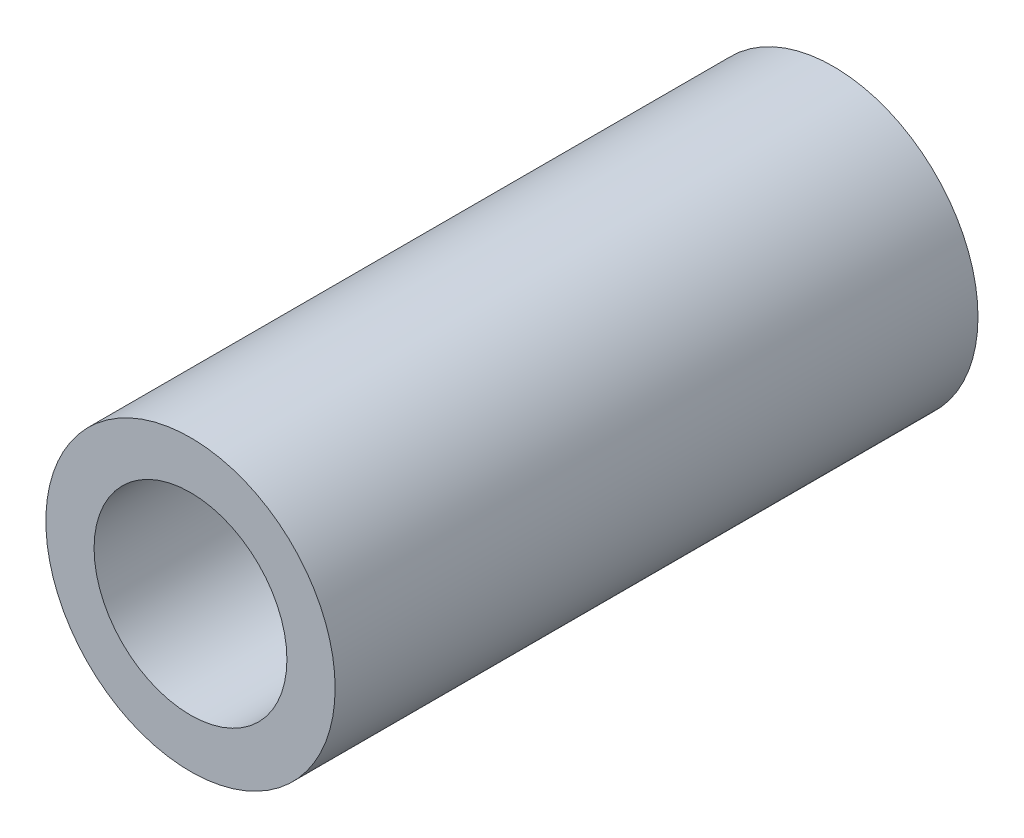
SolidWorks part; units mm, degrees
ref_plane "Front Plane" through (0, 0, 0) normal (0, 0, 1) x (1, 0, 0)
ref_plane "Top Plane" through (0, 0, 0) normal (0, 1, 0) x (1, 0, 0)
ref_plane "Right Plane" through (0, 0, 0) normal (1, 0, 0) x (0, 0, -1)
sketch "Sketch1" plane through (0, 0, 0) normal (0, 0, 1) x (1, 0, 0)
  circle A0 centre (0, 43.1384) radius 4.5
  dimension "D1" = 9
extrude "Boss-Extrude1" add sketch "Sketch1" along normal blind 14 and the other way blind 6 contours A0
sketch "Sketch2" plane through (0, 0, 14) normal (0, 0, 1) x (1, 0, 0)
  circle A0 centre (0, 43.158) radius 3
  dimension "D1" = 6
extrude "Cut-Extrude1" cut sketch "Sketch2" against normal blind 6
